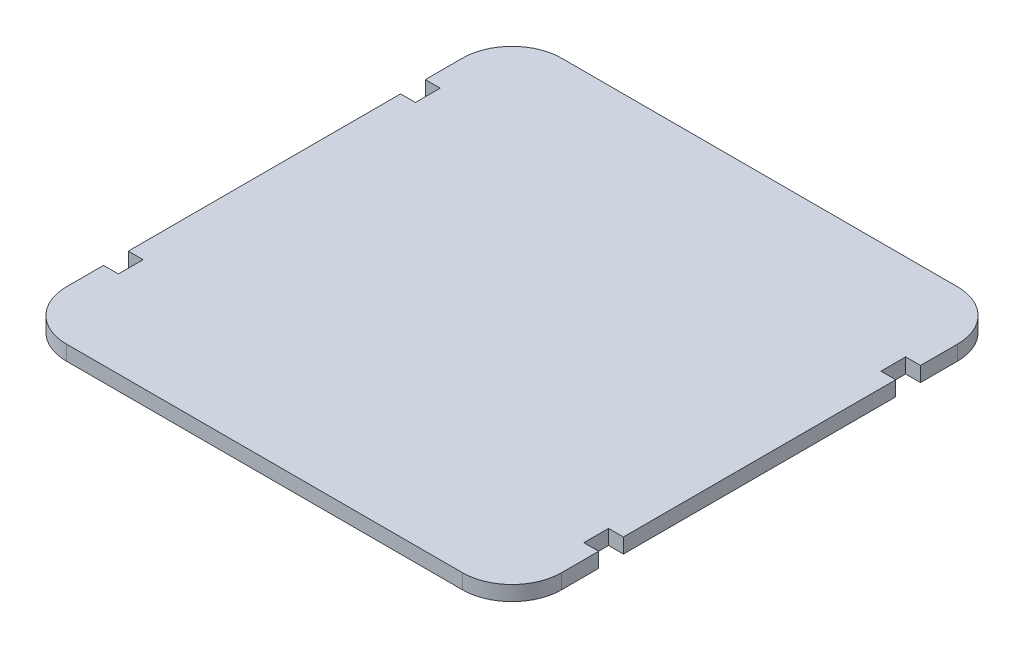
SolidWorks part; units mm, degrees
ref_plane "Front Plane" through (0, 0, 0) normal (0, 0, 1) x (1, 0, 0)
ref_plane "Top Plane" through (0, 0, 0) normal (0, 1, 0) x (1, 0, 0)
ref_plane "Right Plane" through (0, 0, 0) normal (1, 0, 0) x (0, 0, -1)
sketch "Sketch1" plane through (0, 0, 0) normal (0, 1, 0) x (1, 0, 0)
  line L1 (-127, -127) -> (127, -127)
  line L2 (-127, -127) -> (-127, 127)
  line L3 (-127, 127) -> (127, 127)
  line L4 (127, -127) -> (127, 127)
  line L5 (-127, -127) -> (127, 127) construction
  line L6 (-127, 127) -> (127, -127) construction
  point P0 (0, 0)
  dimension "D1" = 254
  dimension "D2" = 254
extrude "Platform-Base" add sketch "Sketch1" along normal blind 7.62
ref_axis "Axis1" through (-127, 7.62, 0) along (0, -1, 0)
ref_plane "Plane1" through (0, 0, 0) normal (0, 0, 1) x (0, -1, 0)
fillet "Corner-Rounding" radius 25.4 4 edges at (-127, 3.81, -127) (127, 3.81, -127) (127, 3.81, 127) (-127, 3.81, 127)
sketch "Sketch8" plane through (0, 7.62, 0) normal (0, 1, 0) x (1, 0, 0)
  line L0 (-127, 0) -> (-127, -76.2) construction
  line L1 (-127, 101.6) -> (-127, -101.6) construction
  line L2 (-127, -76.2) -> (-123.19, -76.2) construction
  line L4 (-119.38, -69.85) -> (-127, -69.85)
  line L5 (-119.38, -69.85) -> (-119.38, -82.55)
  line L6 (-119.38, -82.55) -> (-127, -82.55)
  line L7 (-127, -69.85) -> (-127, -82.55)
  line L8 (-119.38, -69.85) -> (-127, -82.55) construction
  line L9 (-119.38, -82.55) -> (-127, -69.85) construction
  dimension "D1" = 76.2
  dimension "D2" = 7.62
  dimension "D3" = 12.7
extrude "Cut-Extrude4" cut sketch "Sketch8" against normal through all
mirror "Mirror6" about plane through (0, 0, 0) normal (0, 0, 1) of "Cut-Extrude4"
ref_axis "Axis2" through (0, 7.62, 127) along (0, -1, 0)
ref_plane "Plane2" through (0, 0, 0) normal (-1, 0, 0) x (0, -1, 0)
mirror "Mirror7" about plane through (0, 0, 0) normal (-1, 0, 0) of "Mirror6"
equation "\"Foamcore\" = .1in"
equation "\"MDF\" = .3in"
equation "\"Gmaterial\"= \"MDF\""
equation "\"D1@Platform-Base\" = \"Gmaterial\""
equation "\"D2@Sketch8\"=\"Gmaterial\""
